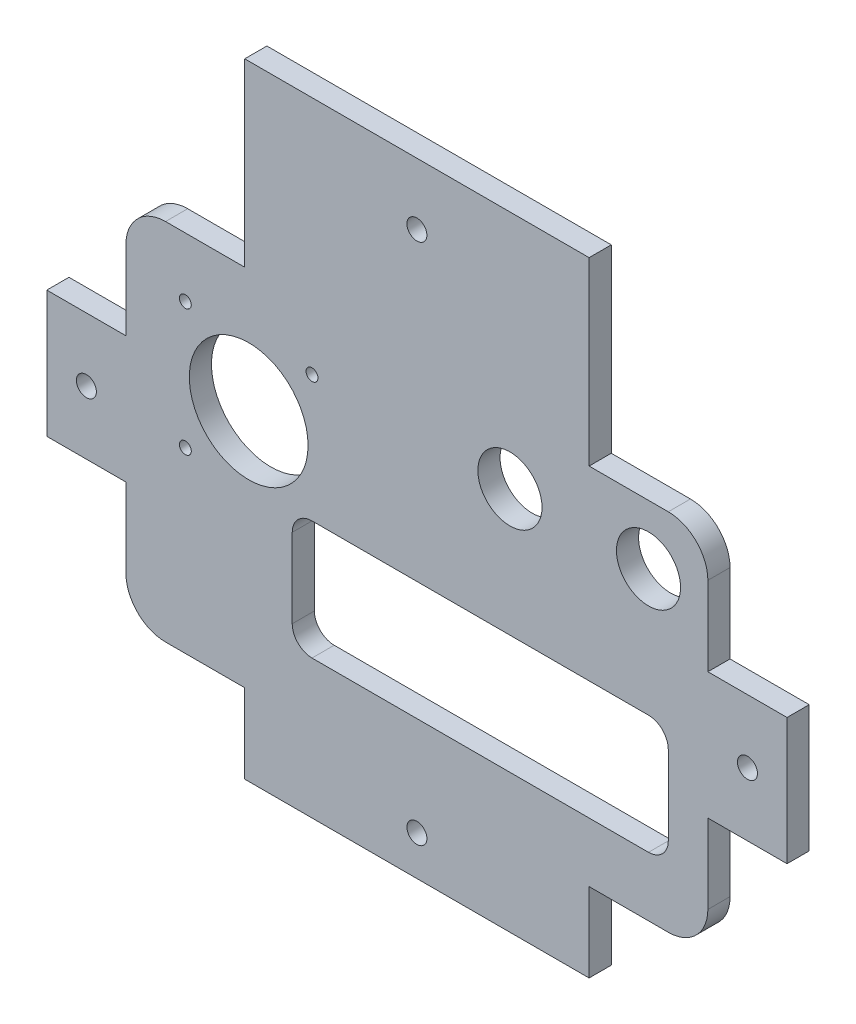
SolidWorks part; units mm, degrees
ref_plane "Front Plane" through (0, 0, 0) normal (0, 0, 1) x (1, 0, 0)
ref_plane "Top Plane" through (0, 0, 0) normal (0, 1, 0) x (1, 0, 0)
ref_plane "Right Plane" through (0, 0, 0) normal (1, 0, 0) x (0, 0, -1)
sketch "Model" plane through (0, 0, 0) normal (0, 0, 1) x (1, 0, 0)
  line L0 (53.1117, 0.7881) -> (-31.8883, 0.7881)
  line L1 (58.1117, -24.2119) -> (58.1117, -4.2119)
  line L2 (-31.8883, -29.2119) -> (53.1117, -29.2119)
  line L3 (-36.8883, -4.2119) -> (-36.8883, -24.2119)
  line L4 (-98.8883, -14.2119) -> (-78.8883, -14.2119)
  line L5 (-78.8883, -14.2119) -> (-78.8883, -34.2119)
  line L6 (-68.8883, -44.2119) -> (-48.8883, -44.2119)
  line L7 (-48.8883, -44.2119) -> (-48.8883, -64.2119)
  line L8 (-48.8883, -64.2119) -> (38.1117, -64.2119)
  line L9 (38.1117, -64.2119) -> (38.1117, -44.2119)
  line L10 (38.1117, -44.2119) -> (58.1117, -44.2119)
  line L11 (68.1117, -34.2119) -> (68.1117, -14.2119)
  line L12 (68.1117, -14.2119) -> (88.1117, -14.2119)
  line L13 (88.1117, -14.2119) -> (88.1117, 17.7881)
  line L14 (88.1117, 17.7881) -> (68.1117, 17.7881)
  line L15 (68.1117, 17.7881) -> (68.1117, 37.7881)
  line L16 (58.1117, 47.7881) -> (38.1117, 47.7881)
  line L17 (38.1117, 47.7881) -> (38.1117, 93.3881)
  line L18 (38.1117, 93.3881) -> (-48.8883, 93.3881)
  line L19 (-48.8883, 93.3881) -> (-48.8883, 47.7881)
  line L20 (-48.8883, 47.7881) -> (-68.8883, 47.7881)
  line L21 (-78.8883, 37.7881) -> (-78.8883, 17.7881)
  line L22 (-78.8883, 17.7881) -> (-98.8883, 17.7881)
  line L23 (-98.8883, 17.7881) -> (-98.8883, -14.2119)
  arc A0 (58.1117, -4.2119) -> (53.1117, 0.7881) centre (53.1117, -4.2119) ccw
  arc A1 (53.1117, -29.2119) -> (58.1117, -24.2119) centre (53.1117, -24.2119) ccw
  arc A2 (-36.8883, -24.2119) -> (-31.8883, -29.2119) centre (-31.8883, -24.2119) ccw
  arc A3 (-31.8883, 0.7881) -> (-36.8883, -4.2119) centre (-31.8883, -4.2119) ccw
  circle A4 centre (18.1117, 32.7881) radius 8.1
  circle A5 centre (-31.8883, 32.7881) radius 1.5
  circle A6 centre (-63.8883, 32.7881) radius 1.5
  circle A7 centre (78.1117, 1.7881) radius 2.525
  circle A8 centre (-5.3883, 77.7881) radius 2.525
  arc A9 (-78.8883, -34.2119) -> (-68.8883, -44.2119) centre (-68.8883, -34.2119) ccw
  arc A10 (58.1117, -44.2119) -> (68.1117, -34.2119) centre (58.1117, -34.2119) ccw
  arc A11 (68.1117, 37.7881) -> (58.1117, 47.7881) centre (58.1117, 37.7881) ccw
  arc A12 (-68.8883, 47.7881) -> (-78.8883, 37.7881) centre (-68.8883, 37.7881) ccw
  circle A13 centre (-88.8883, 1.7881) radius 2.525
  circle A14 centre (-5.3883, -54.2119) radius 2.525
  circle A15 centre (-63.8883, 0.7881) radius 1.5
  circle A16 centre (53.1117, 32.7881) radius 8.1
  circle A17 centre (-47.8883, 16.7881) radius 15
extrude "Boss-Extrude1" add sketch "Model" along normal blind 5.6
